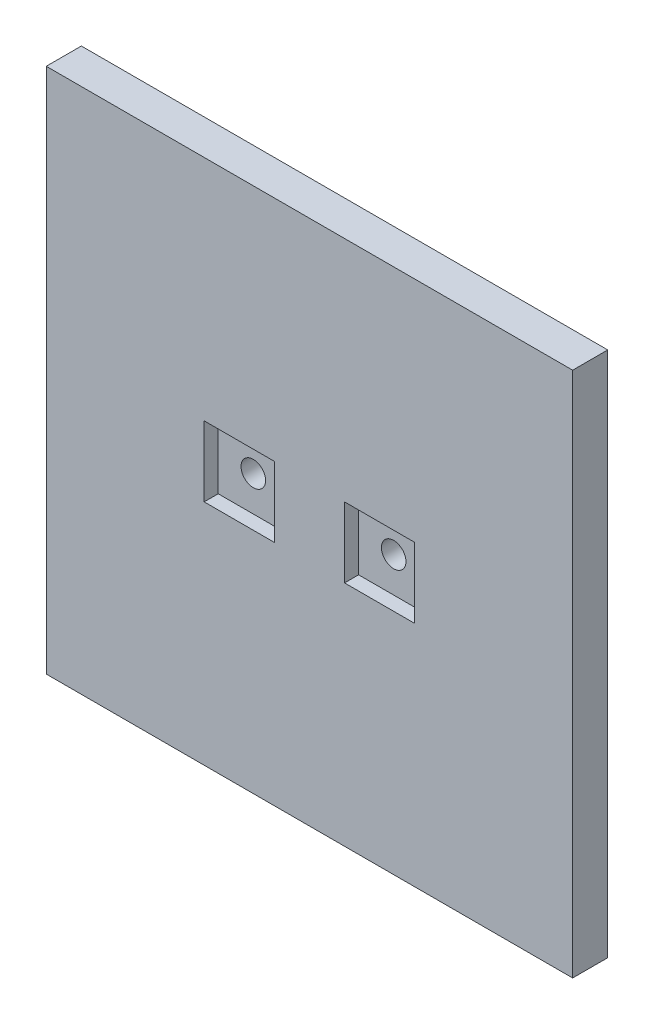
SolidWorks part; units mm, degrees
ref_plane "前视基准面" through (0, 0, 0) normal (0, 0, 1) x (1, 0, 0)
ref_plane "上视基准面" through (0, 0, 0) normal (0, 1, 0) x (1, 0, 0)
ref_plane "右视基准面" through (0, 0, 0) normal (1, 0, 0) x (0, 0, -1)
sketch "草图1" plane through (0, 0, 0) normal (0, 0, 1) x (1, 0, 0)
  line L0 (0, 5) -> (0, -5) construction
  line L5 (-5, -5) -> (5, -5)
  line L6 (-5, -5) -> (-5, 5)
  line L7 (-5, 5) -> (5, 5)
  line L8 (5, -5) -> (5, 5)
  line L9 (-5, -5) -> (5, 5) construction
  line L10 (-5, 5) -> (5, -5) construction
  line L12 (5, 5) -> (15, 5)
  line L13 (5, 5) -> (5, -5)
  line L14 (5, -5) -> (15, -5)
  line L15 (15, 5) -> (15, -5)
  line L16 (-5, 5) -> (-15, 5)
  line L17 (-5, 5) -> (-5, -5)
  line L18 (-5, -5) -> (-15, -5)
  line L19 (-15, 5) -> (-15, -5)
  line L20 (-37.5, 37.5) -> (37.5, 37.5)
  line L21 (-37.5, 37.5) -> (-37.5, -37.5)
  line L22 (-37.5, -37.5) -> (37.5, -37.5)
  line L23 (37.5, 37.5) -> (37.5, -37.5)
  line L24 (-37.5, 37.5) -> (37.5, -37.5) construction
  line L25 (-37.5, -37.5) -> (37.5, 37.5) construction
  circle A3 centre (10, 0) radius 1.75
  circle A4 centre (-10, 0) radius 1.75
  point P0 (0, 0)
  point P16 (0, 0)
  dimension "D3" = 5
  dimension "D4" = 3.5
  dimension "D5" = 5
  dimension "D6" = 5
  dimension "D7" = 5
  dimension "D8" = 75
  dimension "D9" = 75
  dimension "D1" = 10
  dimension "D2" = 10
extrude "凸台-拉伸1" add sketch "草图1" along normal blind 5 contours L23 L20 L21 L22 L19 L16 L7 L12 L15 L14 L5 L18 | L5 L8 L7 L6 region at (0, 0, 0) region at (0, 36.4393, 0)
extrude "凸台-拉伸2" add sketch "草图1<8>" along normal blind 3 contours L16 L19 L18 L6 A4 | L15 L12 L8 L14 A3 region at (-10, -4.8586, 0) region at (5.1414, 0, 0)
sketch "草图1<8>" plane through (0, 0, 0) normal (0, 0, 1) x (1, 0, 0) same geometry as "草图1"
